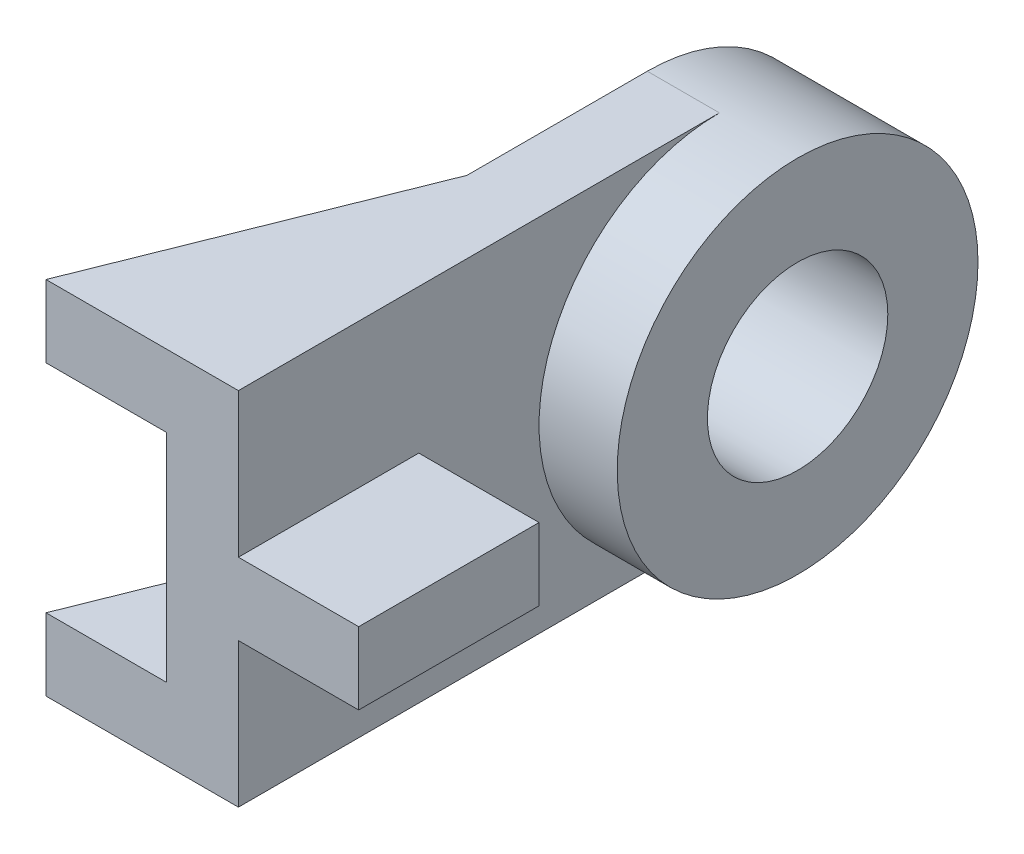
SolidWorks part; units mm, degrees
ref_plane "Front Plane" through (0, 0, 0) normal (1, 0, 0) x (0, 1, 0)
ref_plane "Top Plane" through (0, 0, 0) normal (0, 0, 1) x (0, 1, 0)
ref_plane "Right Plane" through (0, 0, 0) normal (0, 1, 0) x (-1, 0, 0)
sketch "Sketch1" plane through (0, 0, 0) normal (1, 0, 0) x (0, 1, 0)
  line L0 (0, 0) -> (0, 36751.8713) construction
  line L1 (0, 0) -> (36751.8713, 0) construction
  line L2 (-30, 0) -> (-30, 80)
  line L3 (-30, 80) -> (30, 80)
  line L4 (30, 80) -> (30, 0)
  circle A0 centre (0, 0) radius 30
  dimension "D1" = 60
  dimension "D2" = 80
extrude "Boss-Extrude1" add sketch "Sketch1" along normal blind 12 contours A0 L4 L3 L2 region at (0, 0, 51.3838)
extrude "Boss-Extrude2" add sketch "Sketch1<3>" along normal blind 25 contours A0 region at (0, 0, 0)
sketch "Sketch1<3>" plane through (0, 0, 0) normal (1, 0, 0) x (0, 1, 0) same geometry as "Sketch1"
sketch "Sketch2" plane through (0, 0, 0) normal (0, 1, 0) x (-1, 0, 0)
  line L0 (-12, 80) -> (-32, 80)
  line L1 (-32, 80) -> (-32, 50)
  line L2 (-32, 50) -> (-12, 50)
  line L3 (-12, 80) -> (-12, 0) construction
  line L4 (-12, 50) -> (-12, 80)
  dimension "D1" = 30
  dimension "D2" = 20
extrude "Boss-Extrude3" add sketch "Sketch2" along normal mid plane 12
sketch "Sketch3" plane through (0, 30, 0) normal (0, 1, 0) x (-1, 0, 0)
  line L0 (0, 80) -> (20, 80)
  line L1 (20, 80) -> (0, 30)
  line L2 (0, 80) -> (0, 0) construction
  line L3 (0, 30) -> (0, 80)
  dimension "D1" = 20
  dimension "D2" = 50
extrude "Boss-Extrude4" add sketch "Sketch3" against normal blind 12
mirror "Mirror1" about plane through (0, 0, 0) normal (0, 1, 0) of "Boss-Extrude4"
sketch "Sketch4" plane through (25, 0, 0) normal (1, 0, 0) x (0, 1, 0)
  circle A0 centre (0, 0) radius 15
  dimension "D1" = 30
extrude "Cut-Extrude1" cut sketch "Sketch4" against normal through all both and the other way through all
